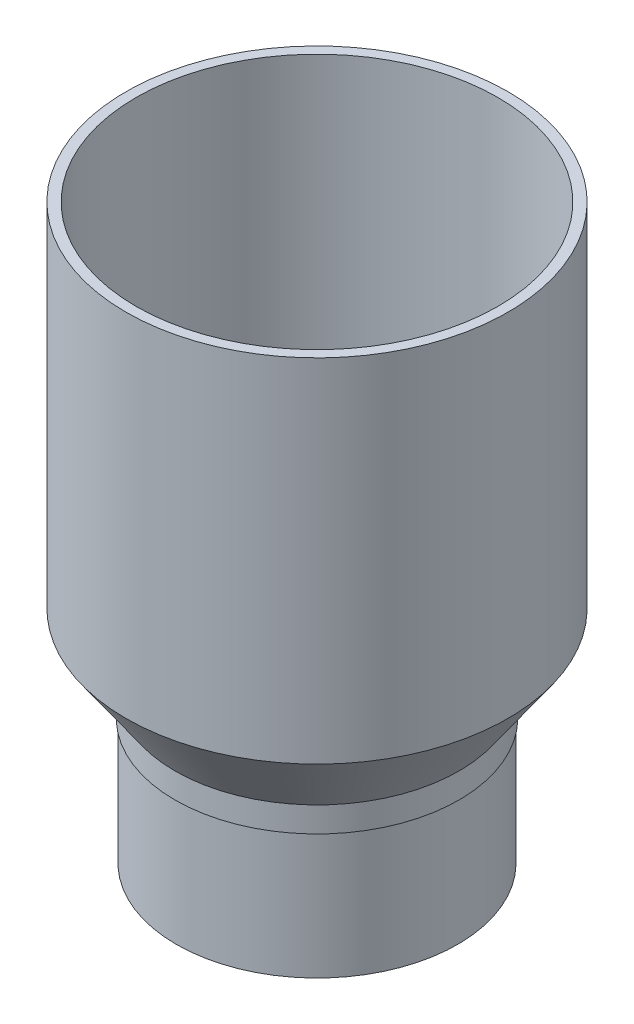
SolidWorks part; units mm, degrees
ref_plane "Front Plane" through (0, 0, 0) normal (0, 0, 1) x (1, 0, 0)
ref_plane "Top Plane" through (0, 0, 0) normal (0, 1, 0) x (1, 0, 0)
ref_plane "Right Plane" through (0, 0, 0) normal (1, 0, 0) x (0, 0, -1)
sketch "Sketch1" plane through (0, 0, 0) normal (0, 0, 1) x (1, 0, 0)
  line L0 (0, 88.7745) -> (0, -57.3806) construction
  line L1 (36, 75.1538) -> (36, 5.1538)
  line L2 (36, 5.1538) -> (26.2492, -8.7718)
  line L3 (26.2492, -8.7718) -> (26.2492, -13.7718)
  line L4 (26.2492, -13.7718) -> (26, -13.7718)
  line L5 (26, -13.7718) -> (26, -38.7718)
  line L6 (36, 75.1538) -> (38, 75.1538)
  line L7 (38, 75.1538) -> (38, 5.1538)
  line L8 (38, 5.1538) -> (28.2492, -8.7718)
  line L9 (28.2492, -8.7718) -> (28.2492, -13.7718)
  line L10 (28.2492, -13.7718) -> (28, -13.7718)
  line L11 (28, -13.7718) -> (28, -38.7718)
  line L12 (26, -38.7718) -> (28, -38.7718)
  point P5 (26, -26.2718)
  point P11 (0, 87.0696)
  point P13 (0, 68.8274)
  point P18 (0, 88.7745)
  dimension "7" = 70
  dimension "D2" = 17
  dimension "D3" = 5
  dimension "D4" = 26
  dimension "D5" = 25
  dimension "D6" = 36
  dimension "D7" = 70
  dimension "D9" = 17
  dimension "D10" = 5
  dimension "D11" = 25
  dimension "D12" = 2
  dimension "D13" = 2
  dimension "D14" = 13.9256
revolve "Revolve1" add sketch "Sketch1" angle 360 about L0
